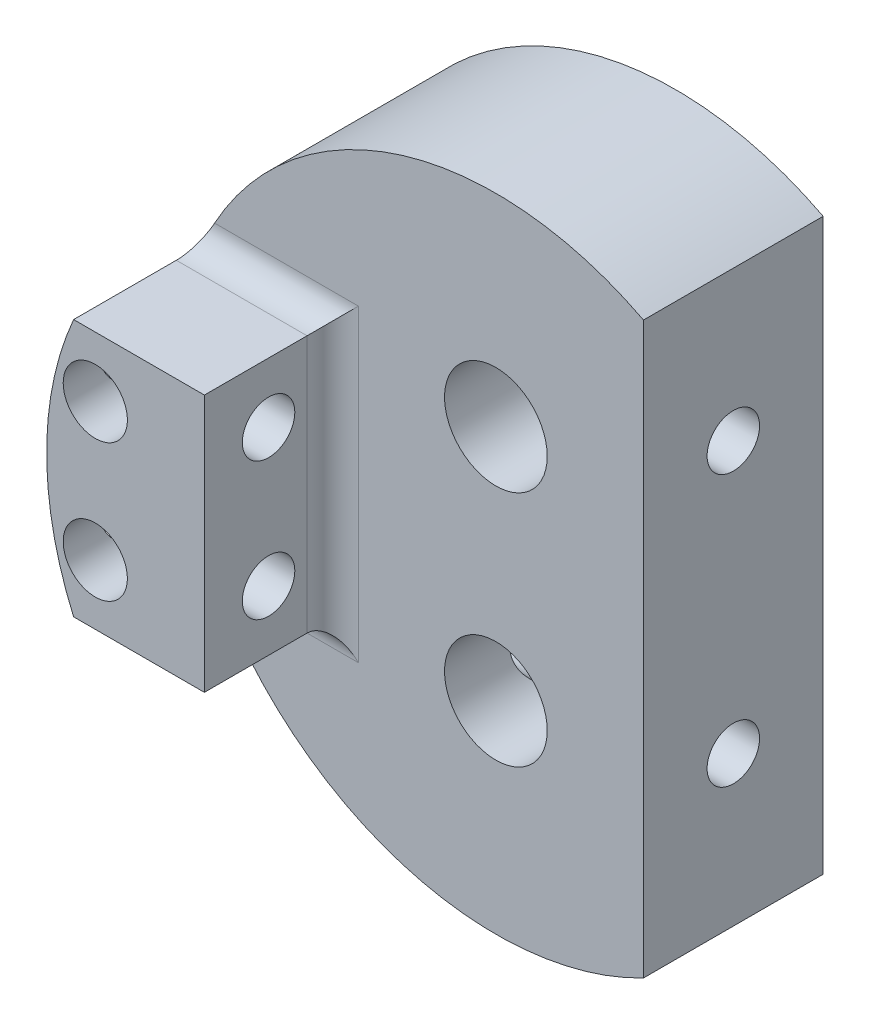
SolidWorks part; units mm, degrees
ref_plane "Front Plane" through (0, 0, 0) normal (1, 0, 0) x (0, 1, 0)
ref_plane "Top Plane" through (0, 0, 0) normal (0, 0, 1) x (0, 1, 0)
ref_plane "Right Plane" through (0, 0, 0) normal (0, 1, 0) x (-1, 0, 0)
sketch "Sketch1" plane through (0, 0, 0) normal (0, 0, 1) x (0, 1, 0)
  line L0 (-23.5, 8.5294) -> (23.5, 8.5294) construction
  line L1 (0, 25) -> (0, -25) construction
  circle A0 centre (0, 0) radius 25
  dimension "D1" = 50
extrude "Boss-Extrude1" add sketch "Sketch1" along normal blind 14
sketch "Sketch2" plane through (0, 0, 14) normal (0, 0, 1) x (0, -1, 0)
  line L0 (0, -25) -> (0, 25) construction
  line L1 (-23.5, -8.5294) -> (23.5, -8.5294)
  arc A0 (-23.5, -8.5294) -> (23.5, -8.5294) centre (0, 0) ccw
extrude "Boss-Extrude2" add sketch "Sketch2" along normal blind 10
sketch "Sketch3" plane through (0, 0, 24) normal (0, 0, 1) x (1, 0, 0)
  line L0 (-20.1507, 0) -> (-20.1507, -3.0861) construction
  line L1 (-25, 0) -> (25, 0) construction
  line L2 (-8.5294, 0) -> (-25, 0) construction
  line L3 (-8.5294, -23.5) -> (-8.5294, 23.5) construction
  line L4 (-21.2113, -2.85) -> (-21.2113, 0) construction
  circle A1 centre (-21.2113, -5.35) radius 2.5
  circle A2 centre (-21.2113, 5.35) radius 2.5
  dimension "D1" = 2.85
extrude "Cut-Extrude1" cut sketch "Sketch3" against normal through all
sketch "Sketch4" plane through (0, 0, 14) normal (0, 0, 1) x (1, 0, 0)
  line L0 (0, -25) -> (0, 25) construction
  line L1 (25, 0) -> (-25, 0) construction
  line L2 (0, 0) -> (0, -5.25) construction
  line L3 (0, -5.25) -> (0, 0)
  circle A0 centre (0, 0) radius 25 construction
  circle A1 centre (0, -9.25) radius 4
  circle A2 centre (0, 9.25) radius 4
  dimension "D1" = 8
extrude "Cut-Extrude2" cut sketch "Sketch4" against normal through all contours A2 | A1 region at (0, -9.25, 14) region at (0, 9.25, 14)
sketch "Sketch5" plane through (-8.5294, 0, 0) normal (1, 0, 0) x (0, 1, 0)
  line L0 (-23.5, 19) -> (23.5, 19) construction
  line L1 (-23.5, 24) -> (-23.5, 14) construction
  line L2 (23.5, 24) -> (23.5, 14) construction
  line L3 (0, 24) -> (0, 14) construction
  line L4 (-23.5, 24) -> (23.5, 24) construction
  line L5 (25, 14) -> (-25, 14) construction
  line L6 (-7.85, 24) -> (-2.85, 24) construction
  line L7 (-13.25, 7) -> (-7.85, 7) construction
  line L8 (-13.25, 14) -> (-13.25, 0) construction
  line L9 (-7.85, 24) -> (-7.85, 0) construction
  circle A0 centre (-5.35, 19) radius 2.045
  circle A1 centre (5.35, 19) radius 2.045
  circle A2 centre (-10.55, 7) radius 2.045
  circle A3 centre (10.55, 7) radius 2.045
  dimension "D1" = 4.09
extrude "M3 Hole for heatset" cut sketch "Sketch5" against normal through all both and the other way through all contours A0 | A1 | A2 | A3 | A0 | A1 | A2 | A3 region at (-8.5294, -5.35, 19) region at (-8.5294, 5.35, 19) region at (-8.5294, -10.55, 7) region at (-8.5294, 10.55, 7)
sketch "Sketch7" plane through (0, 0, 24) normal (0, 0, 1) x (1, 0, 0)
  line L0 (-22.8997, 10.0301) -> (-12.7113, 10.0301)
  line L1 (-8.5294, -23.5) -> (-8.5294, 23.5) construction
  line L2 (-8.5294, 10.0301) -> (-8.5294, 23.5)
  line L3 (-25, 0) -> (-8.5294, 0) construction
  line L4 (-8.5294, -10.0301) -> (-8.5294, -23.5)
  line L5 (-22.8997, -10.0301) -> (-12.7113, -10.0301)
  line L6 (-8.5294, 10.0301) -> (-8.5294, -10.0301)
  line L7 (-18.7113, -5.35) -> (-12.7113, -5.35) construction
  line L8 (-12.7113, 10.0301) -> (-12.7113, -10.0301)
  arc A0 (-22.8997, 10.0301) -> (-8.6579, 23.453) centre (0, 0) cw
  arc A1 (-22.8997, -10.0301) -> (-8.6579, -23.453) centre (0, 0) ccw
  circle A2 centre (-21.2113, -5.35) radius 2.5 construction
  arc M4 (-8.5294, 23.5) -> (-8.5294, -23.5) centre (0, 0) ccw
  line M5 (-8.5294, -23.5) -> (-8.5294, 23.5)
  dimension "D1" = 6
extrude "Cut-Extrude5" cut sketch "Sketch7" against normal blind 10 contours L0 L8 L5 M4 M5 region at (-16.8097, 17.8354, 24)
sketch "Sketch8" plane through (0, 0, 14) normal (0, 0, 1) x (1, 0, 0)
  line L0 (-4, 9.25) -> (4, 9.25)
  line L1 (4, 24.6779) -> (4, -24.6779) construction
  circle A0 centre (0, 9.25) radius 4 construction
  circle A1 centre (0, 0) radius 25 construction
  dimension "D1" = 8
ref_plane "Plane1" through (4, 0, 0) normal (-1, 0, 0) x (0, -1, 0)
sketch "Sketch9" plane through (4, 0, 0) normal (-1, 0, 0) x (0, -1, 0)
  line L1 (-25.9824, 15.6208) -> (26.3443, 15.6208)
  line L2 (-25.9824, 15.6208) -> (-25.9824, -2.6899)
  line L3 (-25.9824, -2.6899) -> (26.3443, -2.6899)
  line L4 (26.3443, 15.6208) -> (26.3443, -2.6899)
  line L5 (-25.9824, 15.6208) -> (26.3443, -2.6899) construction
  line L6 (-25.9824, -2.6899) -> (26.3443, 15.6208) construction
  point P4 (0.1809, 6.4654)
extrude "Cut-Extrude6" cut sketch "Sketch9" against normal blind 21 from offset 7.5 offset against normal yes
sketch "Sketch10" plane through (0, 0, 14) normal (0, 0, 1) x (1, 0, 0)
  line L0 (-4.85, -10.1) -> (-4.85, 10.1)
  line L1 (0, 0) -> (12.414, 0) construction
  line L2 (-15.1, -10.1) -> (-15.1, 10.1)
  line L4 (-15.1, 0) -> (-4.85, 0)
  line L7 (0, -25) -> (0, 25) construction
  line L9 (4, -9.25) -> (4.5, -9.25)
  line L10 (4, 24.6779) -> (4, -24.6779) construction
  line L11 (-25, 0) -> (25, 0) construction
  circle A0 centre (5.099, -18.02) radius 4.1
  arc A1 (-15.1, -10.1) -> (-4.85, -10.1) centre (-9.975, -10.1) ccw
  arc A4 (-15.1, 10.1) -> (-4.85, 10.1) centre (-9.975, 10.1) cw
  circle A5 centre (0, 0) radius 25 construction
  circle A6 centre (0, -9.25) radius 4 construction
  circle A8 centre (6.207, 0) radius 4.1
  circle A9 centre (5.099, 18.02) radius 4.1
  line M26 (-22.8997, 10.0301) -> (-12.7113, 10.0301)
  line M27 (-12.7113, 10.0301) -> (-12.7113, -10.0301)
  line M28 (-12.7113, -10.0301) -> (-22.8997, -10.0301)
  dimension "D2" = 10.25
  dimension "D1" = 8.2
  dimension "D3" = 8.2
extrude "Magnet Slots" cut sketch "Sketch10" along direction (0, 0, 1) on the side of the normal blind 4 from offset 13.8 contours L2 A1 L0 L4 M27 M28 | A0 | A8 | A9 | A4 L2 L4 L0 M26 M27 | L2 L4 M27 M26 | L4 L2 M28 M27 region at (-9.1956, -7.5241, 14) region at (-9.1956, 7.5241, 14) region at (-13.9056, -5.0151, 14) region at (-13.9056, 5.0151, 14) region at (5.099, -18.02, 14) region at (6.207, 0, 14) region at (5.099, 18.02, 14) offset against normal yes
fillet "Fillet1" radius 2 3 edges at (-17.8055, 10.0301, 14) (-12.7113, 0, 14) (-17.8055, -10.0301, 14)
